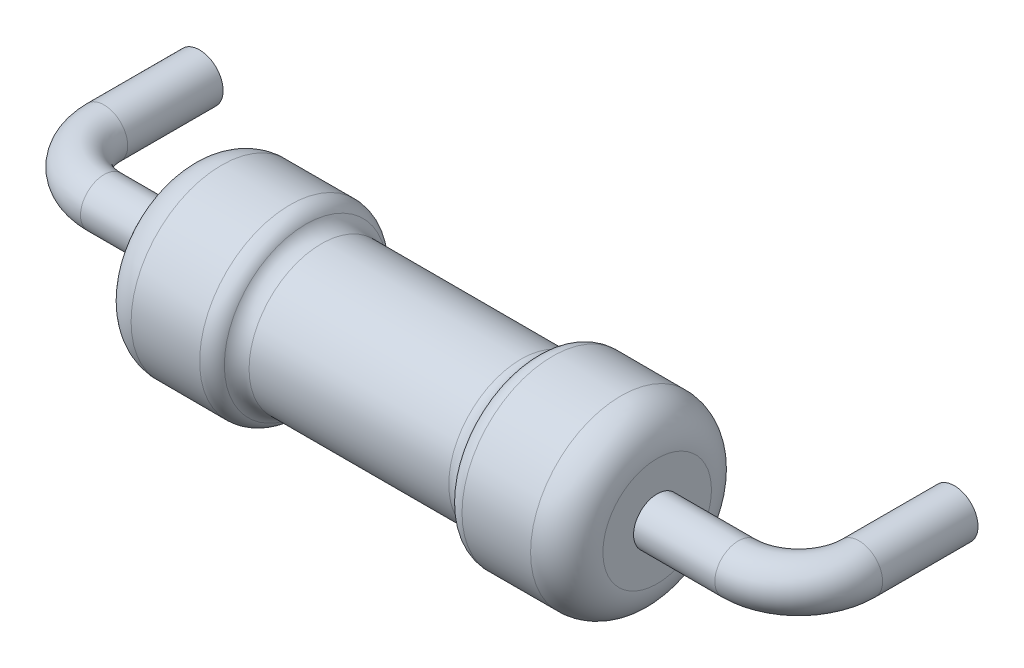
SolidWorks part; units mm, degrees
ref_plane "Спереди" through (0, 0, 0) normal (0, 0, 1) x (1, 0, 0)
ref_plane "Сверху" through (0, 0, 0) normal (0, 1, 0) x (1, 0, 0)
ref_plane "Справа" through (0, 0, 0) normal (1, 0, 0) x (0, 0, -1)
sketch "Эскиз1" plane through (0, 0, 0) normal (0, 0, 1) x (1, 0, 0)
  line L0 (0, 0.2355) -> (0, -0.1957) construction
  circle A0 centre (-4.8, 0) radius 0.3
  point P7 (0, 0)
  dimension "D1" = 0.6
  dimension "D2" = 4.8
sketch "Эскиз3" plane through (0, 0, 0) normal (1, 0, 0) x (0, 0, -1)
  circle A0 centre (-1.38, 0) radius 0.92
  dimension "D1" = 1.84
  dimension "D2" = 1.38
extrude "Бобышка-Вытянуть1" add sketch "Эскиз3" along normal blind 3 from offset 1.5 offset against normal yes
sketch "Эскиз5" plane through (-1.5, 0, 0) normal (-1, 0, 0) x (0, 0, 1)
  circle A0 centre (1.38, 0) radius 1.15
  dimension "D1" = 2.3
extrude "Бобышка-Вытянуть2" add sketch "Эскиз5" along normal blind 1.5
sketch "Эскиз7" plane through (1.5, 0, 0) normal (1, 0, 0) x (0, 0, -1)
  circle A0 centre (-1.38, 0) radius 1.15
  dimension "D1" = 2.3
extrude "Бобышка-Вытянуть3" add sketch "Эскиз7" along normal blind 1.5
fillet "Скругление1" radius 0.46 2 edges at (3, 0, 0.23) (-3, 0, 2.53)
fillet "Скругление3" radius 0.23 2 edges at (-1.5, 0, 2.3) (1.5, 0, 0.46)
fillet "Скругление4" radius 0.23 2 edges at (1.5, 0, 0.23) (-1.5, 0, 2.53)
sketch "Эскиз10" plane through (0, 0, 0) normal (0, 1, 0) x (1, 0, 0)
  line L1 (-4.8, 0) -> (-4.8, -0.6133)
  line L2 (-5.1, 0) -> (-4.5, 0) construction
  line L3 (-3, -1.38) -> (-4.0333, -1.38)
  line L4 (-3, -0.69) -> (-3, -2.07) construction
  arc A0 (-4.8, -0.6133) -> (-4.0333, -1.38) centre (-4.0333, -0.6133) ccw
  dimension "D1" = 0.7667
sweep "По траектории8" add profiles "Эскиз1" path "Эскиз10"
mirror "Зеркальное отражение1" about plane through (0, 0, 0) normal (1, 0, 0) of bodies 106
sketch "Эскиз32" plane through (0, 0, 0) normal (0, 0, -1) x (-1, 0, 0)
  circle A0 centre (4.8, 0) radius 0.3
  circle A1 centre (-4.8, 0) radius 0.3
  dimension "D1" = 0.6
  dimension "D2" = 0.6
extrude "Бобышка-Вытянуть4" add sketch "Эскиз32" along normal blind 0.6
equation "\"H\" = 6"
equation "\"D1@Эскиз1\"=\"d1\""
equation "\"d\" = 2.3"
equation "\"L\"= 28"
equation "\"d1\" = 0.6"
equation "\"D2@Эскиз1\"=\"H\"/2+\"H\"*0.3"
equation "\"D1@Эскиз3\"=\"d\"*0.8"
equation "\"D2@Эскиз3\"=\"d\"*0.6"
equation "\"D1@Бобышка-Вытянуть1\"=\"H\"/2"
equation "\"D19@Бобышка-Вытянуть1\"=\"H\"/4"
equation "\"D1@Эскиз5\"=\"d\""
equation "\"D1@Бобышка-Вытянуть2\"=\"H\"/4"
equation "\"D1@Бобышка-Вытянуть3\"=\"H\"/4"
equation "\"D1@Скругление1\"=\"d\"*0.2"
equation "\"D1@Скругление3\"=\"d\"*0.1"
equation "\"D1@Скругление4\"=\"d\"*0.1"
equation "\"D1@Эскиз10\"=\"d\"/3"
equation "\"D1@Бобышка-Вытянуть4\"=\"d1\""
equation "\"D1@Эскиз7\"=\"d\""
equation "\"D1@Эскиз32\"=\"d1\""
equation "\"D2@Эскиз32\"=\"d1\""
